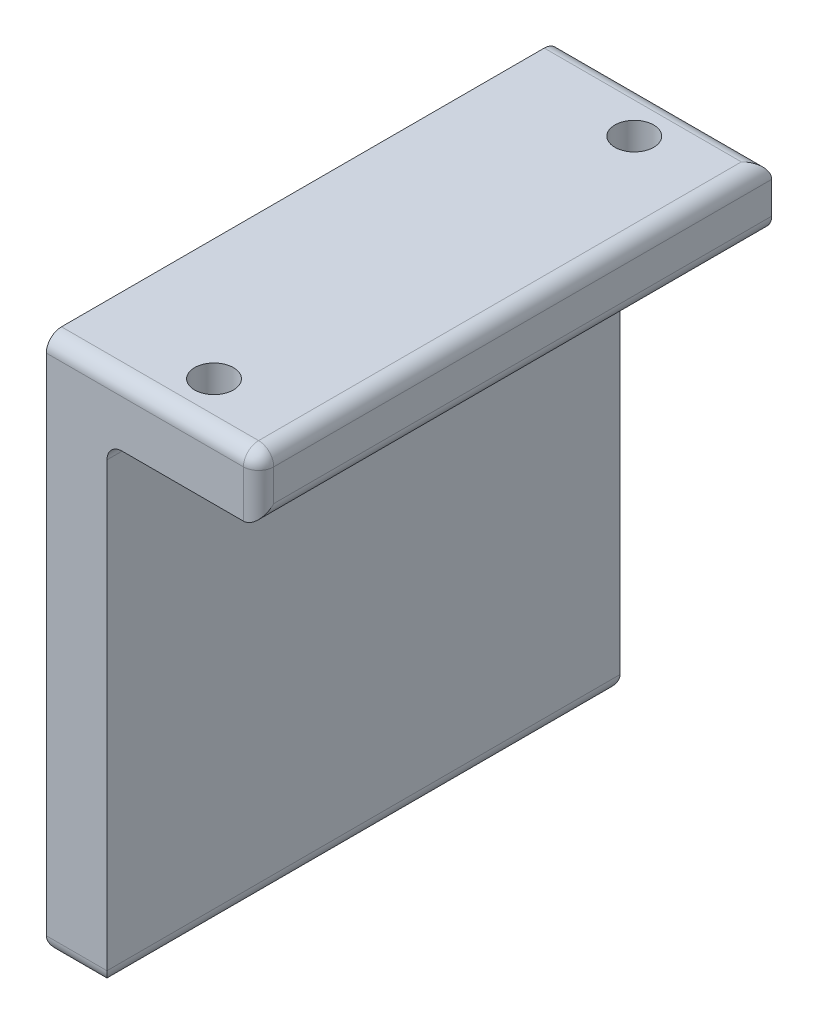
SolidWorks part; units mm, degrees
ref_plane "Front Plane" through (0, 0, 0) normal (0, 0, 1) x (1, 0, 0)
ref_plane "Top Plane" through (0, 0, 0) normal (0, 1, 0) x (1, 0, 0)
ref_plane "Right Plane" through (0, 0, 0) normal (1, 0, 0) x (0, 0, -1)
sketch "Sketch1" plane through (0, 0, 0) normal (1, 0, 0) x (0, 0, -1)
  line L0 (-173.99, 224.028) -> (-173.99, 183.134)
  line L1 (-214.884, -224.028) -> (214.884, -224.028)
  line L2 (-214.884, -224.028) -> (-214.884, 224.028)
  line L3 (-214.884, 224.028) -> (214.884, 224.028)
  line L4 (214.884, -224.028) -> (214.884, 224.028)
  line L5 (-214.884, -224.028) -> (214.884, 224.028) construction
  line L6 (-214.884, 224.028) -> (214.884, -224.028) construction
  line L7 (0, 224.028) -> (0, -224.028) construction
  line L8 (-214.884, 0) -> (214.884, 0) construction
  circle A4 centre (-173.99, 183.134) radius 16.256
  circle A5 centre (173.99, 183.134) radius 16.256
  point P0 (0, 0)
  dimension "D4" = 40.894
  dimension "D5" = 32.512
  dimension "D1" = 448.056
  dimension "D2" = 429.768
  dimension "D3" = 40.894
extrude "Boss-Extrude1" add sketch "Sketch1" along normal blind 50.8 contours A4 L2 L1 L4 L3 region at (0, -1.5928, 0)
sketch "Sketch2" plane through (50.8, 0, 0) normal (1, 0, 0) x (0, 0, -1)
  line L0 (214.884, -224.028) -> (214.884, 224.028) construction
  line L1 (-214.884, 224.028) -> (214.884, 224.028)
  line L2 (-214.884, 224.028) -> (-214.884, 171.958)
  line L3 (-214.884, 171.958) -> (214.884, 171.958)
  line L4 (214.884, 224.028) -> (214.884, 171.958)
  dimension "D1" = 52.07
extrude "Boss-Extrude2" add sketch "Sketch2" along normal blind 127
sketch "Sketch3" plane through (0, 224.028, 0) normal (0, 1, 0) x (1, 0, 0)
  line L0 (0, -214.884) -> (0, 214.884) construction
  line L1 (177.8, 214.884) -> (0, 214.884) construction
  line L3 (0, 0) -> (177.8, 0) construction
  line L4 (177.8, 214.884) -> (177.8, -214.884) construction
  line L5 (88.9, 214.884) -> (101.6, 176.012)
  circle A0 centre (101.6, 176.012) radius 16.256
  circle A1 centre (101.6, -176.012) radius 16.256
  dimension "D2" = 32.512
  dimension "D1" = 40.894
  dimension "D3" = 101.6
extrude "Cut-Extrude1" cut sketch "Sketch3" against normal blind 76.2 contours A0 | A1 region at (92.3256, 224.028, -163.2251) region at (101.6, 224.028, 176.012)
fillet "Fillet1" radius 12.7 10 edges at (88.9, 224.028, -214.884) (88.9, 224.028, 214.884) (25.4, -224.028, 214.884) (25.4, -224.028, -214.884) (177.8, 197.993, 214.884) (177.8, 224.028, 0) (177.8, 171.958, 0) (50.8, 171.958, 0) (50.8, -224.028, 0) (0, -224.028, 0)
